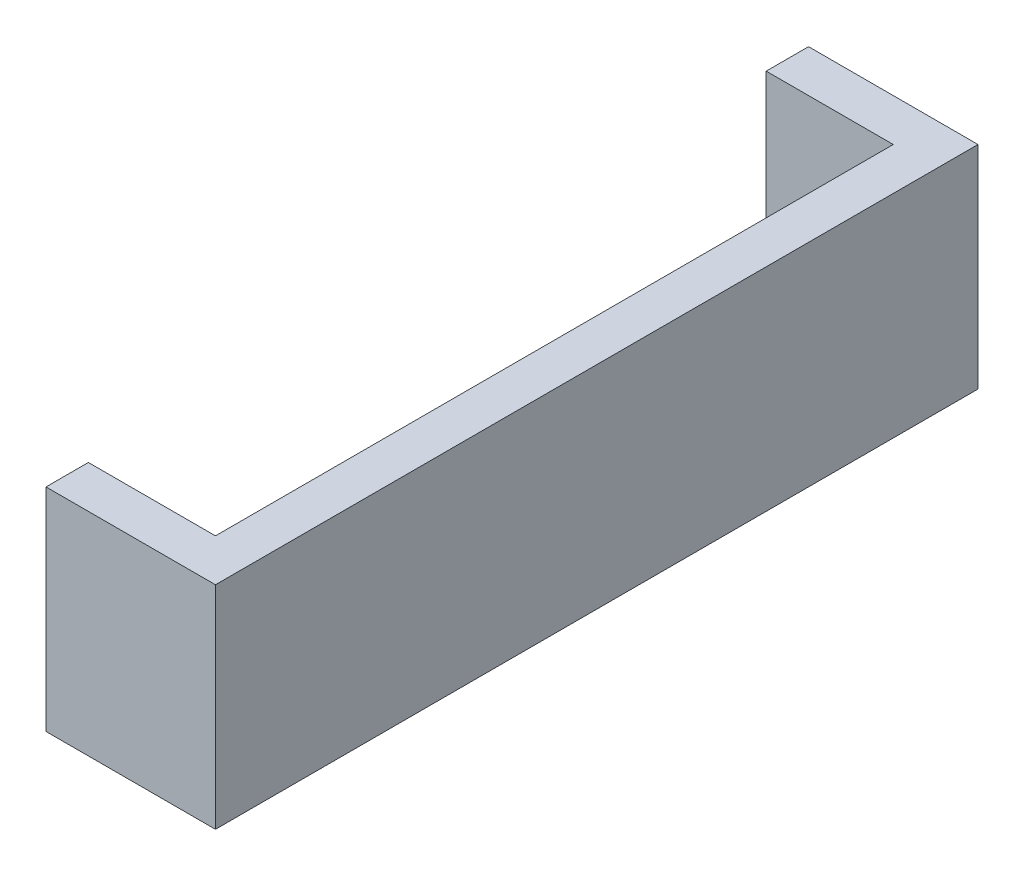
SolidWorks part; units mm, degrees
ref_plane "Front Plane" through (0, 0, 0) normal (0, 0, 1) x (1, 0, 0)
ref_plane "Top Plane" through (0, 0, 0) normal (0, 1, 0) x (1, 0, 0)
ref_plane "Right Plane" through (0, 0, 0) normal (1, 0, 0) x (0, 0, -1)
sketch "Sketch1" plane through (0, 0, 0) normal (0, 1, 0) x (1, 0, 0)
  line L1 (-12.7, -57.15) -> (12.7, -57.15)
  line L2 (-12.7, -57.15) -> (-12.7, 57.15)
  line L3 (-12.7, 57.15) -> (12.7, 57.15)
  line L4 (12.7, -57.15) -> (12.7, 57.15)
  line L5 (-12.7, -57.15) -> (12.7, 57.15) construction
  line L6 (-12.7, 57.15) -> (12.7, -57.15) construction
  point P0 (0, 0)
  point P5 (0, 0)
  dimension "D1" = 25.4
  dimension "D2" = 114.3
extrude "Boss-Extrude1" add sketch "Sketch1" along normal blind 6.35
sketch "Sketch3" plane through (0, 6.35, 0) normal (0, 1, 0) x (1, 0, 0)
  line L0 (12.7, -57.15) -> (12.7, 57.15) construction
  line L1 (-12.7, 57.15) -> (12.7, 57.15)
  line L2 (-12.7, 57.15) -> (-12.7, 50.8)
  line L3 (-12.7, 50.8) -> (12.7, 50.8)
  line L4 (12.7, 57.15) -> (12.7, 50.8)
  line L6 (-12.7, -57.15) -> (12.7, -57.15)
  line L7 (-12.7, -57.15) -> (-12.7, -50.8)
  line L8 (-12.7, -50.8) -> (12.7, -50.8)
  line L9 (12.7, -57.15) -> (12.7, -50.8)
  dimension "D1" = 6.35
extrude "Boss-Extrude2" add sketch "Sketch3" along normal blind 25.4
sketch "Sketch6" plane through (0, 6.35, 0) normal (0, 1, 0) x (1, 0, 0)
  line L0 (12.7, -50.8) -> (12.7, 50.8) construction
  line L1 (12.7, 38.1) -> (19.05, 38.1)
  line L2 (12.7, 38.1) -> (12.7, 25.4)
  line L3 (12.7, 25.4) -> (19.05, 25.4)
  line L5 (12.7, 57.15) -> (-12.7, 57.15) construction
  line L6 (19.05, 44.45) -> (25.4, 44.45)
  line L7 (19.05, 44.45) -> (19.05, 38.1)
  line L8 (19.05, 19.05) -> (25.4, 19.05)
  line L9 (25.4, 44.45) -> (25.4, 19.05)
  line L10 (19.05, 25.4) -> (19.05, 19.05)
  point P10 (25.4, 31.75)
  point P11 (12.7, 31.75)
  dimension "D1" = 6.35
  dimension "D2" = 12.7
  dimension "D3" = 25.4
  dimension "D4" = 6.35
  dimension "D5" = 25.4
extrude "Boss-Extrude3" add sketch "Sketch6" against normal up to surface (6.35 mm away) up to face at (0, 0, 0)
sketch "Sketch7" plane through (0, 6.35, 0) normal (0, 1, 0) x (1, 0, 0)
  line L0 (-12.7, 50.8) -> (-12.7, -50.8) construction
  line L1 (-12.7, 38.1) -> (-6.35, 38.1)
  line L2 (-12.7, 38.1) -> (-12.7, 25.4)
  line L3 (-12.7, 25.4) -> (-6.35, 25.4)
  line L5 (-6.35, 25.4) -> (-6.35, 19.05)
  line L6 (0, 44.45) -> (-6.35, 44.45)
  line L7 (0, 44.45) -> (0, 19.05)
  line L8 (0, 19.05) -> (-6.35, 19.05)
  line L9 (-6.35, 44.45) -> (-6.35, 38.1)
  line L10 (19.05, 38.1) -> (12.7, 38.1) construction
  line L11 (25.4, 44.45) -> (19.05, 44.45) construction
  line L12 (19.05, 44.45) -> (19.05, 38.1) construction
  line L13 (25.4, 19.05) -> (25.4, 44.45) construction
extrude "Cut-Extrude2" cut sketch "Sketch7" against normal through all
mirror "Mirror1" about plane through (0, 0, 0) normal (0, 0, 1) of "Boss-Extrude3", "Cut-Extrude2"
sketch "Sketch8" plane through (0, 6.35, 0) normal (0, 1, 0) x (1, 0, 0)
  line L0 (-12.7, -57.15) -> (12.7, -57.15) construction
  line L1 (12.7, 57.15) -> (25.4, 57.15)
  line L2 (12.7, 57.15) -> (12.7, -57.15)
  line L3 (12.7, -57.15) -> (25.4, -57.15)
  line L4 (25.4, 57.15) -> (25.4, -57.15)
  line L5 (25.4, 19.05) -> (25.4, 44.45) construction
extrude "Cut-Extrude3" cut sketch "Sketch8" against normal through all
sketch "Sketch9" plane through (0, 6.35, 0) normal (0, 1, 0) x (1, 0, 0)
  line L0 (12.7, -50.8) -> (-12.7, -50.8) construction
  line L1 (12.7, 50.8) -> (6.35, 50.8)
  line L2 (12.7, 50.8) -> (12.7, -50.8)
  line L3 (12.7, -50.8) -> (6.35, -50.8)
  line L4 (6.35, 50.8) -> (6.35, -50.8)
  line L5 (-12.7, -50.8) -> (-12.7, -57.15) construction
extrude "Boss-Extrude4" add sketch "Sketch9" along normal up to surface (25.4 mm away) up to face at (0, 31.75, 53.975)
